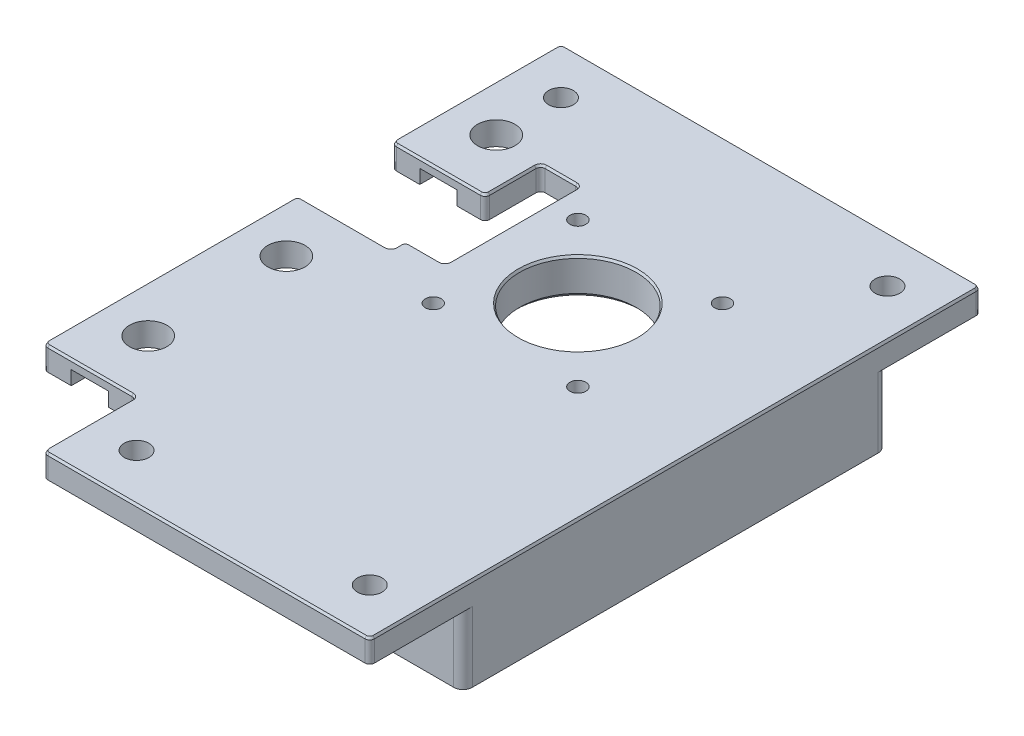
SolidWorks part; units mm, degrees
ref_plane "Front" through (0, 0, 0) normal (0, 0, 1) x (1, 0, 0)
ref_plane "Top" through (0, 0, 0) normal (0, 1, 0) x (1, 0, 0)
ref_plane "Right" through (0, 0, 0) normal (1, 0, 0) x (0, 0, -1)
sketch "Sketch1" plane through (0, 0, 0) normal (0, 1, 0) x (1, 0, 0)
  line L1 (0, 0) -> (90, 0)
  line L2 (0, 0) -> (0, 131)
  line L3 (0, 131) -> (90, 131)
  line L4 (90, 0) -> (90, 131)
  dimension "D1" = 90
  dimension "D2" = 131
extrude "Boss-Extrude1" add sketch "Sketch1" along normal blind 5
sketch "Sketch2" plane through (0, 5, 0) normal (0, 1, 0) x (1, 0, 0)
  line L0 (0, 94.625) -> (20, 94.625)
  line L1 (0, 131) -> (0, 0) construction
  line L2 (20, 94.625) -> (20, 91.625)
  line L3 (20, 91.625) -> (28.5, 91.625)
  line L4 (28.5, 91.625) -> (28.5, 77.625)
  line L5 (28.5, 77.625) -> (20, 77.625)
  line L6 (20, 77.625) -> (20, 74.625)
  line L7 (20, 74.625) -> (0, 74.625)
  line L8 (0, 74.625) -> (0, 94.625)
  line L9 (50, 84.625) -> (56.9971, 84.625) construction
  line L10 (0, 0) -> (20, 0)
  line L11 (0, 0) -> (0, 20)
  line L12 (0, 20) -> (20, 20)
  line L13 (20, 0) -> (20, 20)
  line L15 (90, 131) -> (0, 131) construction
  line L28 (28.5, 106.125) -> (28.5, 91.625) construction
  line L29 (34.5, 69.125) -> (65.5, 69.125) construction
  line L30 (34.5, 69.125) -> (34.5, 100.125) construction
  line L31 (34.5, 100.125) -> (65.5, 100.125) construction
  line L32 (65.5, 69.125) -> (65.5, 100.125) construction
  line L33 (34.5, 69.125) -> (65.5, 100.125) construction
  line L34 (34.5, 100.125) -> (65.5, 69.125) construction
  line L35 (71.5, 63.125) -> (28.5, 63.125) construction
  line L36 (71.5, 63.125) -> (71.5, 106.125) construction
  line L37 (71.5, 106.125) -> (28.5, 106.125) construction
  line L38 (28.5, 63.125) -> (28.5, 106.125) construction
  line L39 (71.5, 63.125) -> (28.5, 106.125) construction
  line L40 (71.5, 106.125) -> (28.5, 63.125) construction
  line L41 (28.5, 77.625) -> (28.5, 63.125) construction
  line L48 (32, 59.625) -> (68, 59.625) construction
  line L49 (32, 59.625) -> (32, 109.625) construction
  line L50 (32, 109.625) -> (68, 109.625) construction
  line L51 (68, 59.625) -> (68, 109.625) construction
  line L52 (32, 59.625) -> (68, 109.625) construction
  line L53 (32, 109.625) -> (68, 59.625) construction
  circle A0 centre (50, 84.625) radius 12.5
  circle A2 centre (65.5, 100.125) radius 1.7
  circle A3 centre (34.5, 100.125) radius 1.7
  circle A4 centre (65.5, 69.125) radius 1.7
  circle A5 centre (34.5, 69.125) radius 1.7
  circle A10 centre (32, 109.625) radius 1.7 construction
  circle A11 centre (68, 109.625) radius 1.7 construction
  circle A12 centre (68, 59.625) radius 1.7 construction
  circle A13 centre (32, 59.625) radius 1.7 construction
  point P14 (28.5, 84.625)
  point P54 (50, 84.625)
  dimension "D5" = 25
  dimension "D9" = 3.4
  dimension "D12" = 3.4
  dimension "D1" = 20
  dimension "D2" = 14
  dimension "D3" = 43
  dimension "D4" = 3
  dimension "D6" = 50
  dimension "D7" = 46.375
  dimension "D8" = 31
  dimension "D10" = 50
  dimension "D11" = 36
  dimension "D13" = 20
extrude "Cut-Extrude1" cut sketch "Sketch2" against normal up to next
hole_wizard "M5 Clearance Hole1" positions "Sketch3" profile "Sketch4" hole size "M5" standard "ANSI Metric" end condition through all
sketch "Sketch3" plane through (0, 5, 0) normal (0, 1, 0) x (1, 0, 0)
  line L0 (10, 20) -> (10, 131) construction
  line L1 (20, 20) -> (0, 20) construction
  line L2 (90, 131) -> (0, 131) construction
  line L5 (20, 10) -> (142.2662, 10) construction
  line L6 (20, 0) -> (20, 20) construction
  line L10 (0, 121) -> (90, 121) construction
  line L11 (0, 131) -> (0, 94.625) construction
  line L12 (90, 0) -> (90, 131) construction
  line L14 (20, 0) -> (90, 0) construction
  line L15 (0, 74.625) -> (0, 20) construction
  line L16 (90, 0) -> (90, 131) construction
  line L17 (90, 111) -> (0, 111) construction
  line L18 (90, 0) -> (90, 131) construction
  line L19 (20, 131) -> (20, 20) construction
  point P31 (10, 121)
  point P37 (80, 121)
  point P42 (30, 10)
  point P45 (80, 10)
  dimension "D1" = 10
  dimension "D2" = 10
  dimension "D3" = 10
  dimension "D4" = 10
  dimension "D5" = 10
  dimension "D6" = 10
  dimension "D7" = 20
sketch "Sketch4" plane through (80, 5, -10) normal (1, 0, 0) x (0, 0, 1)
  line L0 (0, 0) -> (0, 5)
  line L1 (0, 5) -> (2.65, 5)
  line L2 (2.65, 5) -> (2.65, 0)
  line L5 (2.65, 0) -> (0, 0)
  line L11 (0, -6.35) -> (0, 107.95) construction
  dimension "Thru Hole Dia." = 5.3
  dimension "Thru Hole Depth" = 5
sketch "Sketch6" plane through (0, 0, 0) normal (0, -1, 0) x (-1, 0, 0)
  line L0 (-20, 20) -> (0, 20) construction
  line L1 (0, 74.625) -> (-20, 74.625) construction
  line L2 (0, 74.625) -> (0, 20) construction
  line L3 (-20, 94.625) -> (0, 94.625) construction
  line L4 (0, 131) -> (0, 94.625) construction
  circle A0 centre (-10, 32.5) radius 4
  circle A1 centre (-10, 62.125) radius 4
  circle A2 centre (-10, 107.125) radius 4
  dimension "D2" = 8
  dimension "D1" = 12.5
  dimension "D3" = 12.5
  dimension "D4" = 10
  dimension "D5" = 10
  dimension "D6" = 12.5
  dimension "D7" = 10
extrude "Cut-Extrude2" cut sketch "Sketch6" against normal blind 10
other "Move Face1" flip direction yes face at (10, 2.5, -94.625) face at (10, 2.5, -74.625) offset 0.1 parameters "D1"=0.1
sketch "Sketch9" plane through (0, 0, 0) normal (0, -1, 0) x (1, 0, 0)
  line L0 (90, -111) -> (90, -20)
  line L1 (90, 0) -> (90, -131) construction
  line L2 (90, -20) -> (20, -20)
  line L3 (20, -20) -> (20, -74.525)
  line L4 (90, -111) -> (71, -111)
  line L5 (90, -131) -> (0, -131) construction
  line L6 (71, -111) -> (71, -106)
  line L7 (71, -106) -> (85, -106)
  line L8 (85, -106) -> (85, -25)
  line L9 (85, -25) -> (25, -25)
  line L10 (25, -25) -> (25, -74.525)
  line L11 (25, -74.525) -> (20, -74.525)
  line L12 (20, 0) -> (90, 0) construction
  line L13 (0, -74.525) -> (20, -74.525) construction
  line L14 (20, -74.525) -> (20, -77.625) construction
  dimension "D1" = 20
  dimension "D2" = 5
  dimension "D3" = 20
  dimension "D4" = 5
  dimension "D7" = 19
  dimension "D8" = 5
extrude "Boss-Extrude2" add sketch "Sketch9" along normal blind 15
fillet "Fillet4" radius 3 3 edges at (25, -7.5, -25) (85, -7.5, -25) (85, -7.5, -106)
fillet "Fillet5" radius 2 7 edges at (90, -7.5, -20) (90, -7.5, -111) (71, -7.5, -111) (71, -7.5, -106) (20, -7.5, -20) (25, -7.5, -74.525) (20, -7.5, -74.525)
ref_plane "Plane1" through (10, 0, 0) normal (-1, 0, 0) x (0, 0, 1)
sketch "Sketch10" plane through (10, 0, 0) normal (-1, 0, 0) x (0, 0, 1)
  line L0 (-74.525, 0) -> (-74.525, 3)
  line L1 (-28, 0) -> (-103, 0) construction
  line L2 (-74.525, 0) -> (-74.525, 5) construction
  line L3 (-74.525, 3) -> (-71.525, 0)
  line L5 (-71.525, 0) -> (-74.525, 0)
  line L6 (-97.725, 0) -> (-94.725, 0)
  line L8 (-94.725, 0) -> (-94.725, 3)
  line L10 (-94.725, 3) -> (-97.725, 0)
  line L11 (-20, 0) -> (-23, 0)
  line L13 (-20, 0) -> (0, 0) construction
  line L16 (-20, 0) -> (-20, 3)
  line L17 (-20, 0) -> (-20, 5) construction
  line L18 (-20, 3) -> (-23, 0)
  line L21 (-94.725, 0) -> (-94.725, 5) construction
  dimension "D1" = 45
  dimension "D2" = 3
extrude "Cut-Extrude5" cut sketch "Sketch10" against normal blind 4 and the other way blind 4
sketch "Sketch11" plane through (0, 5, 0) normal (0, 1, 0) x (1, 0, 0)
  line L5 (28.5, 77.625) -> (28.5, 91.625) construction
  line L6 (20, 91.625) -> (28.5, 91.625)
  line L7 (20, 91.625) -> (20, 106.625)
  line L8 (20, 106.625) -> (28.5, 106.625)
  line L9 (28.5, 91.625) -> (28.5, 106.625)
  dimension "D1" = 15
extrude "Cut-Extrude6" cut sketch "Sketch11" against normal through all
fillet "Fillet6" radius 1 14 edges at (28.5, 2.5, -77.625) (90, 2.5, 0) (90, 2.5, -131) (0, 2.5, -131) (0, 2.5, -94.725) (20, 2.5, -74.525) (20, 2.5, -77.625) (0, 2.5, -74.525) (0, 2.5, -20) (20, 2.5, 0) (20, 2.5, -20) (28.5, 2.5, -106.625) (20, 2.5, -94.725) (20, 2.5, -106.625)
sketch "Sketch15" plane through (0, 0, 0) normal (0, -1, 0) x (1, 0, 0)
  line L0 (29.5, -100.125) -> (29.5, -69.125)
  line L1 (34.5, -64.125) -> (65.5, -64.125)
  line L2 (70.5, -69.125) -> (70.5, -100.125)
  line L3 (34.5, -105.125) -> (65.5, -105.125)
  circle A0 centre (65.5, -100.125) radius 1.7 construction
  circle A1 centre (34.5, -100.125) radius 1.7 construction
  circle A2 centre (65.5, -69.125) radius 1.7 construction
  circle A3 centre (34.5, -69.125) radius 1.7 construction
  circle A4 centre (65.5, -100.125) radius 1.7
  circle A5 centre (34.5, -100.125) radius 1.7
  circle A6 centre (65.5, -69.125) radius 1.7
  circle A7 centre (34.5, -69.125) radius 1.7
  circle A8 centre (50, -84.625) radius 12.5 construction
  circle A9 centre (50, -84.625) radius 12.5
  circle A10 centre (34.5, -69.125) radius 5 construction
  circle A11 centre (34.5, -100.125) radius 5 construction
  circle A12 centre (65.5, -100.125) radius 5 construction
  circle A13 centre (65.5, -69.125) radius 5 construction
  arc A14 (29.5, -100.125) -> (34.5, -105.125) centre (34.5, -100.125) ccw
  arc A15 (29.5, -69.125) -> (34.5, -64.125) centre (34.5, -69.125) cw
  arc A16 (65.5, -64.125) -> (70.5, -69.125) centre (65.5, -69.125) cw
  arc A17 (70.5, -100.125) -> (65.5, -105.125) centre (65.5, -100.125) cw
  dimension "D1" = 10
extrude "Boss-Extrude3" add sketch "Sketch15" along normal blind 3
chamfer "Chamfer1" distance 1 angle 45 9 edges at (50, -3, -97.125) (70.5, 0, -84.625) (69.0355, 0, -65.5895) (69.0355, 0, -103.6605) (50, 0, -64.125) (50, 0, -105.125) (30.9645, 0, -65.5895) (30.9645, 0, -103.6605) (29.5, 0, -84.625)
chamfer "Printability Chamfer" distance 0.5 angle 30 29 edges at (24.25, 5, -77.625) (20.2929, 5, -77.3321) (28.2071, 5, -77.9179) (20, 5, -76.075) (28.5, 5, -92.125) (19.7071, 5, -74.8179) (28.2071, 5, -106.3321) (10, 5, -74.525) (24.25, 5, -106.625) (0.2929, 5, -74.2321) (20.2929, 5, -106.3321) (0, 5, -47.2625) (20, 5, -100.675) (0.2929, 5, -20.2929) (19.7071, 5, -95.0179) (10, 5, -20) (10, 5, -94.725) (19.7071, 5, -19.7071) (0.2929, 5, -95.0179) (20, 5, -10) (0, 5, -112.8625) (20.2929, 5, -0.2929) (0.2929, 5, -130.7071) (55, 5, 0) (45, 5, -131) (89.7071, 5, -0.2929) (89.7071, 5, -130.7071) (90, 5, -65.5) (50, 5, -72.125) first distance on face at (24.25, 2.5, -77.625) first distance on face at (20.3964, 2.5, -77.2286) first distance on face at (28.1036, 2.5, -78.0214) first distance on face at (20, 2.5, -76.075) first distance on face at (28.5, 2, -93.725) first distance on face at (19.6036, 2.5, -74.9214) first distance on face at (28.1036, 2.5, -106.2286) first distance on face at (10, 2, -74.525) first distance on face at (24.25, 2.5, -106.625) first distance on face at (0.3964, 2.5, -74.1286) first distance on face at (20.3964, 2.5, -106.2286) first distance on face at (0, 2.5, -47.2625) first distance on face at (20, 2.5, -100.675) first distance on face at (0.3964, 2.5, -20.3964) first distance on face at (19.6036, 2.5, -95.1214) first distance on face at (10, 2, -20) first distance on face at (10, 2, -94.725) first distance on face at (19.6036, 2.5, -19.6036) first distance on face at (0.3964, 2.5, -95.1214) first distance on face at (20, 2.5, -10) first distance on face at (0, 2.5, -112.8625) first distance on face at (20.3964, 2.5, -0.3964) first distance on face at (0.3964, 2.5, -130.6036) first distance on face at (55, 2.5, 0) first distance on face at (45, 2.5, -131) first distance on face at (89.6036, 2.5, -0.3964) first distance on face at (89.6036, 2.5, -130.6036) first distance on face at (90, -2.5, -65.5) first distance on face at (50, -2, -97.125)
mirror "Mirror1" [suppressed] of bodies 114 108
delete or keep bodies "Body-Delete/Keep 1" [suppressed] type delete bodies bodies 114
sketch "Sketch12" plane through (0, 5, 0) normal (1, 0, 0) x (0, -1, 0)
  line L0 (4.4, 131) -> (4.4, 94.725) construction
  line L4 (5, 131) -> (0.5, 131) construction
  line L5 (5, 130) -> (5, 95.725) construction
  line L6 (0.5, 94.725) -> (5, 94.725) construction
  text T0 "LZP-03" font "Century Gothic" height in points 12
  dimension "D1" = 0.6
extrude "Left Part Num" cut sketch "Sketch12" along normal blind 0.4
sketch "Sketch13" [suppressed] plane through (180, -175, 0) normal (-1, 0, 0) x (0, 1, 0)
  line L0 (175.6, 94.725) -> (175.6, 131) construction
  line L4 (175, 131) -> (179.5, 131) construction
  line L5 (179.5, 94.725) -> (175, 94.725) construction
  line L6 (175, 130) -> (175, 95.725) construction
  text T0 "RZP-03" font "Century Gothic" height in points 12
  dimension "D1" = 0.6
extrude "Right Part Num" [suppressed] cut sketch "Sketch13" along normal blind 0.4
equation "\"D3@Sketch6\"=\"D1@Sketch6\""
equation "\"D6@Sketch6\"=\"D1@Sketch6\""
equation "\"D8@Sketch9\"=\"D4@Sketch9\""
equation "\"D2@Sketch9\"=\"D4@Sketch9\""
